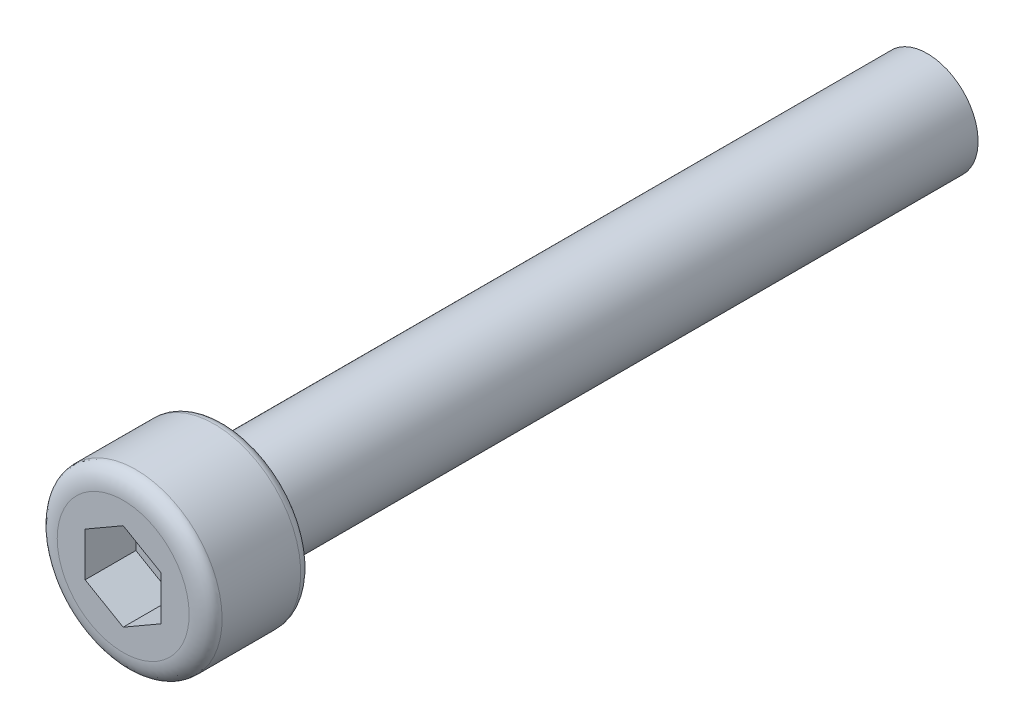
SolidWorks part; units mm, degrees
ref_plane "前视基准面" through (0, 0, 0) normal (0, 0, 1) x (1, 0, 0)
ref_plane "上视基准面" through (0, 0, 0) normal (0, 1, 0) x (1, 0, 0)
ref_plane "右视基准面" through (0, 0, 0) normal (1, 0, 0) x (0, 0, -1)
sketch "草图2" plane through (0, 0, 0) normal (1, 0, 0) x (0, 0, -1)
  line L0 (-16, 0) -> (-16, 3.4)
  line L1 (-16, 3.4) -> (-12, 3.4)
  line L2 (-12, 3.4) -> (-12, 2)
  line L3 (-12, 2) -> (16, 2)
  line L4 (16, 2) -> (16, 0)
  line L5 (16, 0) -> (-16, 0)
  dimension "D1" = 28
  dimension "D2" = 3.4
  dimension "D3" = 2
  dimension "D4" = 4
revolve "旋转1" add sketch "草图2" angle 360 about L5
chamfer "倒角1" distance 0.3 angle 60 1 edges at (-2, 0, -16) first distance on face at (-2, 0, 12)
fillet "圆角1" radius 0.4 1 edges at (-3.4, 0, 12)
fillet "圆角2" radius 0.8 1 edges at (-3.4, 0, 16) second distance 0.5 first distance on face at (-3.4, 0, 16)
sketch "草图3" plane through (0, 0, 16) normal (0, 0, 1) x (1, 0, 0)
  line L1 (0, 1.7321) -> (-1.5, 0.866)
  line L2 (-1.5, 0.866) -> (-1.5, -0.866)
  line L3 (-1.5, -0.866) -> (0, -1.7321)
  line L4 (0, -1.7321) -> (1.5, -0.866)
  line L5 (1.5, -0.866) -> (1.5, 0.866)
  line L6 (1.5, 0.866) -> (0, 1.7321)
  circle A0 centre (0, 0) radius 1.5 construction
  dimension "D1" = 3
extrude "切除-拉伸1" cut sketch "草图3" against normal blind 2
